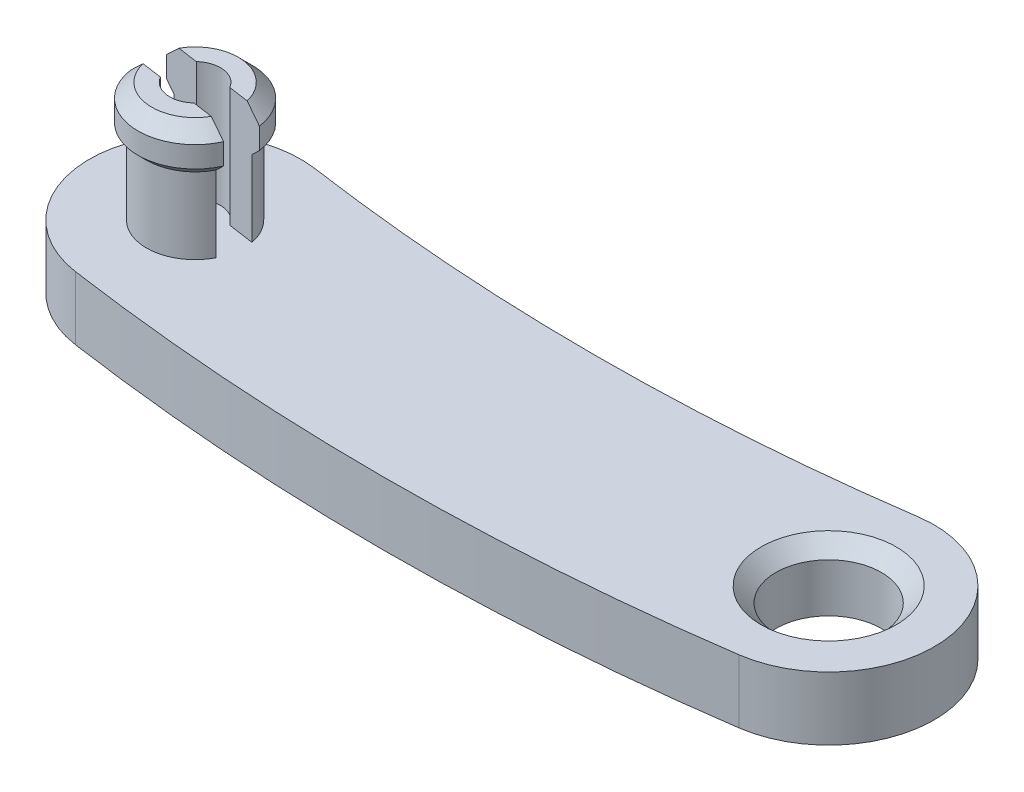
SolidWorks part; units mm, degrees
ref_plane "Front Plane" through (0, 0, 0) normal (0, 0, 1) x (1, 0, 0)
ref_plane "Top Plane" through (0, 0, 0) normal (0, 1, 0) x (1, 0, 0)
ref_plane "Right Plane" through (0, 0, 0) normal (1, 0, 0) x (0, 0, -1)
sketch "Sketch1" plane through (0, 0, 0) normal (0, 1, 0) x (1, 0, 0)
  line L0 (0, 0) -> (-30, 0) construction
  circle A0 centre (0, 0) radius 2.5 construction
  circle A1 centre (0, 0) radius 5
  circle A2 centre (-30, 0) radius 2.5 construction
  circle A3 centre (-30, 0) radius 5
  arc A4 (-0.7143, 4.9487) -> (-29.2857, 4.9487) centre (-15, 103.923) cw
  arc A5 (0.7143, -4.9487) -> (-30.7143, -4.9487) centre (-15, 103.923) cw
  dimension "D1" = 5
  dimension "D2" = 10
  dimension "D4" = 100
  dimension "D5" = 110
  dimension "D3" = 30
extrude "Boss-Extrude1" add sketch "Sketch1" against normal blind 3 contours A3 | A5 A1 A4 A3 | A1 region at (0, 0, 0) region at (-15, 0, 0.9711) region at (-30, 0, 0)
sketch "Sketch2" plane through (0, 0, 0) normal (0, 1, 0) x (1, 0, 0)
  circle A0 centre (0, 0) radius 2.5
  circle A1 centre (-30, 0) radius 2.5 construction
  dimension "D1" = 5
extrude "Cut-Extrude1" cut sketch "Sketch2" against normal up to surface (3 mm away) up to face at (-15, -3, 0.1813)
chamfer "Chamfer1" distance 0.7 1 edges at (0, 0, 2.5)
sketch "Sketch3" plane through (0, 0, 0) normal (0, 1, 0) x (1, 0, 0)
  circle A0 centre (-30, 0) radius 2.5 construction
  circle A1 centre (-30, 0) radius 2.3
  dimension "D1" = 5
  dimension "D2" = 4.6
extrude "Boss-Extrude2" add sketch "Sketch3" along normal blind 4
sketch "Sketch4" plane through (0, 4, 0) normal (0, 1, 0) x (1, 0, 0)
  circle A0 centre (-30, 0) radius 2.7
  dimension "D1" = 5.4
extrude "Boss-Extrude3" add sketch "Sketch4" along normal blind 1
chamfer "Chamfer2" distance 0.4 angle 45 1 edges at (-30, 4, 2.3)
sketch "Sketch5" plane through (0, 5, 0) normal (0, 1, 0) x (1, 0, 0)
  circle A0 centre (-30, 0) radius 2.05
  dimension "D1" = 4.1
extrude "Boss-Extrude4" add sketch "Sketch5" along normal blind 0.65
chamfer "Chamfer3" distance 0.65 angle 45 1 edges at (-30, 5, 2.05)
sketch "Sketch6" plane through (0, 5.65, 0) normal (0, 1, 0) x (1, 0, 0)
  line L0 (-15, 103.923) -> (-31.347, -9.3322) construction
  line L1 (-30.1071, -0.7423) -> (-29.8929, 0.7423) construction
  line L3 (-34.9999, -0.0361) -> (-25.2144, -1.4485)
  line L4 (-34.7856, 1.4485) -> (-25.0001, 0.0361)
  circle A0 centre (-30, 0) radius 5
  arc A1 (-29.2857, 4.9487) -> (-30.7143, -4.9487) centre (-30, 0) ccw construction
  circle A2 centre (0, 0) radius 5 construction
  arc A3 (0.7143, -4.9487) -> (-0.7143, 4.9487) centre (0, 0) ccw construction
  arc A6 (-43.4405, 2.8481) -> (11.8029, 2.4016) centre (-15, 103.923) ccw construction
  point P23 (-30, 0)
  circle M2 centre (-30, 0) radius 2.05
  dimension "D1" = 1.5
  dimension "D3" = 105
extrude "Cut-Extrude2" cut sketch "Sketch6" against normal up to surface (5.65 mm away) contours L3 A0 L4 M2 | L4 L3 M2 | L4 A0 L3 M2 region at (-33.4562, 5.65, -0.4989) region at (-30, 5.65, 0) region at (-26.5438, 5.65, 0.4989) up to face at (-30, 0, 2.3)
sketch "Sketch7" plane through (0, 5.65, 0) normal (0, 1, 0) x (1, 0, 0)
  circle A0 centre (-30, 0) radius 1.2
  dimension "D1" = 2.4
extrude "Cut-Extrude3" cut sketch "Sketch7" against normal up to surface (5.65 mm away) up to face at (-30.2179, 0, 1.5094)
